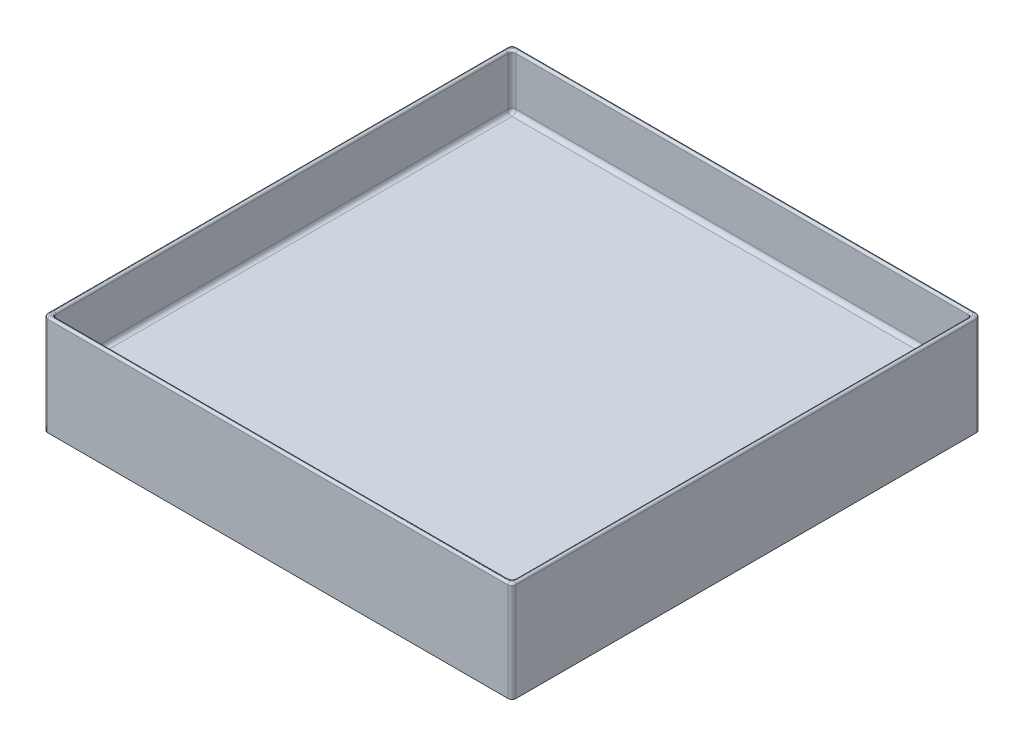
SolidWorks part; units mm, degrees
ref_plane "Front Plane" through (0, 0, 0) normal (0, 0, 1) x (1, 0, 0)
ref_plane "Top Plane" through (0, 0, 0) normal (0, 1, 0) x (1, 0, 0)
ref_plane "Right Plane" through (0, 0, 0) normal (1, 0, 0) x (0, 0, -1)
sketch "Sketch1" plane through (0, 0, 0) normal (0, 1, 0) x (1, 0, 0)
  line L1 (-280, 280) -> (280, 280)
  line L2 (-280, 280) -> (-280, -280)
  line L3 (-280, -280) -> (280, -280)
  line L4 (280, 280) -> (280, -280)
  line L5 (-280, 280) -> (280, -280) construction
  line L6 (-280, -280) -> (280, 280) construction
  point P0 (0, 0)
  dimension "D1" = 560
  dimension "D2" = 560
extrude "Boss-Extrude1" add sketch "Sketch1" along normal blind 5
sketch "Sketch2" plane through (0, 5, 0) normal (0, 1, 0) x (1, 0, 0)
  line L1 (-275, 275) -> (275, 275)
  line L2 (-275, 275) -> (-275, -275)
  line L3 (-275, -275) -> (275, -275)
  line L4 (280, -280) -> (280, 280)
  line L5 (280, 280) -> (-280, 280)
  line L6 (-280, 280) -> (-280, -280)
  line L7 (-280, -280) -> (280, -280)
  line L8 (280, -280) -> (280, 280)
  line L9 (280, 280) -> (-280, 280)
  line L10 (-280, 280) -> (-280, -280)
  line L11 (-280, -280) -> (280, -280)
  line L12 (275, 275) -> (275, -275)
  line L13 (-275, 275) -> (275, -275) construction
  line L14 (-275, -275) -> (275, 275) construction
  point P2 (0, 0)
  dimension "D2" = 5
  dimension "D3" = 5
  dimension "D1" = 0
extrude "Boss-Extrude2" add sketch "Sketch2" along normal blind 65
extrude "Boss-Extrude3" add sketch "Sketch2<2>" against normal blind 50 from offset 5 offset against normal yes
sketch "Sketch2<2>" plane through (0, 5, 0) normal (0, 1, 0) x (1, 0, 0) same geometry as "Sketch2"
ref_plane "Plane1" through (0, -30, 0) normal (0, -1, 0) x (-1, 0, 0)
sketch "Sketch7" plane through (0, -30, 0) normal (0, -1, 0) x (-1, 0, 0)
  line L1 (-50, 100) -> (50, 100)
  line L2 (-50, 100) -> (-50, -100)
  line L3 (-50, -100) -> (50, -100)
  line L4 (50, 100) -> (50, -100)
  line L5 (-50, 100) -> (50, -100) construction
  line L6 (-50, -100) -> (50, 100) construction
  point P0 (0, 0)
  dimension "D1" = 100
  dimension "D2" = 200
extrude "Boss-Extrude5" add sketch "Sketch7" along normal blind 5 separate body
sketch "Sketch8" plane through (0, 0, -100) normal (0, 0, -1) x (-1, 0, 0)
  line L0 (275, 0) -> (-275, 0) construction
  line L1 (-50, -35) -> (50, -35)
  line L2 (-50, -35) -> (-50, 0)
  line L3 (-50, 0) -> (50, 0)
  line L4 (50, -35) -> (50, 0)
  dimension "D1" = 100
extrude "Boss-Extrude6" add sketch "Sketch8" along normal blind 5
ref_plane "Plane2" through (0, 0, 0) normal (0, 0, -1) x (-1, 0, 0)
mirror "Mirror1" about plane through (0, 0, 0) normal (0, 0, -1) of "Boss-Extrude6"
sketch "Sketch9" plane through (0, -35, 0) normal (0, -1, 0) x (1, 0, 0)
  line L1 (0, 40) -> (7.5, 52.9904) construction
  line L2 (7.5, 52.9904) -> (-7.5, 52.9904) construction
  line L3 (-7.5, 52.9904) -> (0, 40) construction
  circle A0 centre (0, 48.6603) radius 4.3301 construction
  circle A1 centre (7.5, 52.9904) radius 3
  circle A2 centre (0, 40) radius 3
  circle A3 centre (-7.5, 52.9904) radius 3
  dimension "D3" = 6
  dimension "D1" = 15
  dimension "D2" = 40
extrude "Cut-Extrude1" cut sketch "Sketch9" against normal blind 5
fillet "Fillet1" radius 5 20 edges at (-275, -25, -275) (275, -25, -275) (275, -25, 275) (-275, -25, 275) (275, 37.5, -275) (275, 37.5, 275) (-275, 37.5, 275) (-275, 37.5, -275) (0, 5, -275) (-275, 5, 0) (275, 5, 0) (0, 5, 275) (-275, 0, 0) (0, 0, -275) (275, 0, 0) (0, 0, 275) (0, 0, -105) (0, -35, -105) (0, -35, 105) (0, 0, 105)
fillet "Fillet2" radius 2.5 12 edges at (-273.5355, 70, -273.5355) (-275, 70, 0) (-273.5355, 70, 273.5355) (0, 70, 275) (273.5355, 70, 273.5355) (275, 70, 0) (273.5355, 70, -273.5355) (0, 70, -275) (-280, 70, 0) (0, 70, -280) (280, 70, 0) (0, 70, 280)
fillet "Fillet3" radius 5 8 edges at (-279.2678, 69.2678, 279.2678) (279.2678, 69.2678, 279.2678) (279.2678, 69.2678, -279.2678) (-279.2678, 69.2678, -279.2678) (-280, 8.75, -280) (280, 8.75, -280) (280, 8.75, 280) (-280, 8.75, 280)
